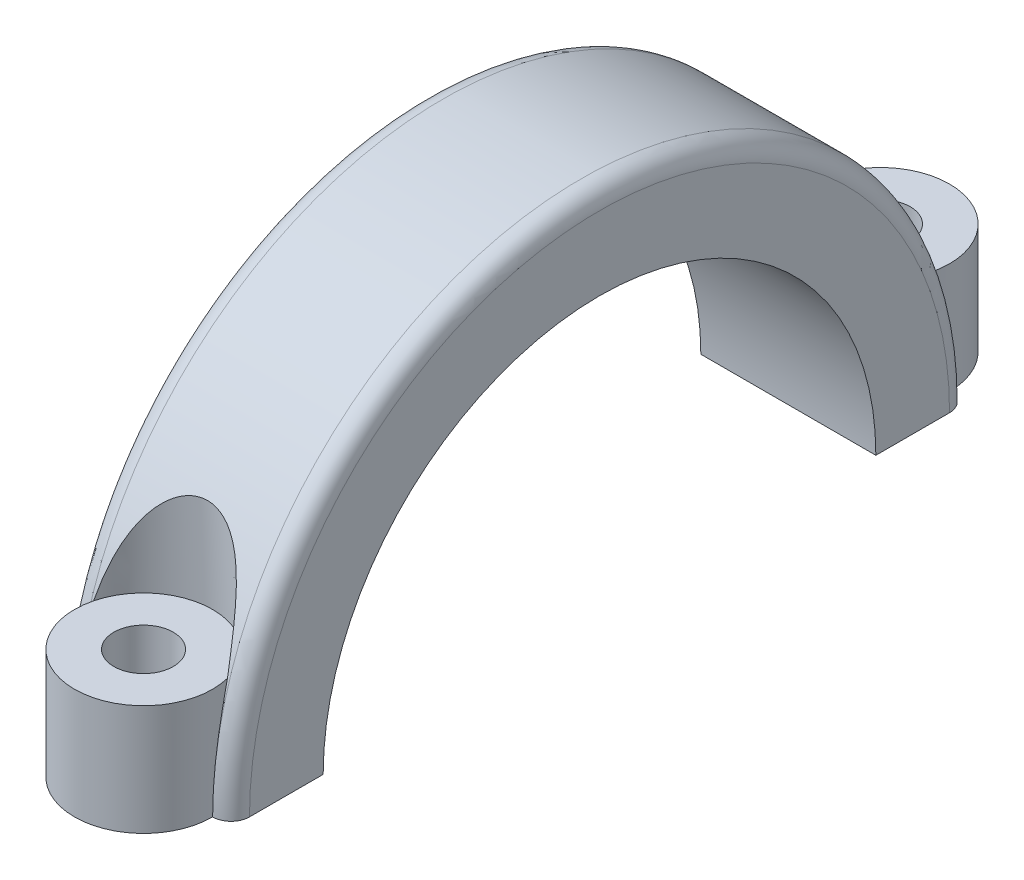
SolidWorks part; units mm, degrees
ref_plane "Front Plane" through (0, 0, 0) normal (0, 0, 1) x (1, 0, 0)
ref_plane "Top Plane" through (0, 0, 0) normal (0, 1, 0) x (1, 0, 0)
ref_plane "Right Plane" through (0, 0, 0) normal (1, 0, 0) x (0, 0, -1)
sketch "Sketch1" plane through (0, 0, 0) normal (1, 0, 0) x (0, 0, -1)
  line L0 (-50.8, 0) -> (-38.1, 0)
  line L1 (38.1, 0) -> (50.8, 0)
  arc A0 (38.1, 0) -> (-38.1, 0) centre (0, 0) ccw
  arc A1 (50.8, 0) -> (-50.8, 0) centre (0, 0) ccw
  circle A3 centre (0, 0) radius 38.1 construction
  circle A4 centre (0, 0) radius 50.8 construction
  point P1 (50.8, 0)
  point P7 (36.4352, 11.1394)
  dimension "D1" = 76.2
  dimension "D2" = 12.7
extrude "Boss-Extrude1" add sketch "Sketch1" along normal mid plane 24.13
sketch "Sketch2" plane through (0, 0, 0) normal (0, -1, 0) x (1, 0, 0)
  line L0 (12.065, -50.8) -> (-12.065, -50.8) construction
  circle A0 centre (0, -50.8) radius 9.525
  dimension "D1" = 19.05
extrude "Boss-Extrude2" add sketch "Sketch2" against normal blind 15.25
extrude "Cut-Extrude1" cut sketch "Sketch2<2>" against normal blind 15.25 draft 3 from offset 15.25 offset against normal yes
sketch "Sketch2<2>" plane through (0, 0, 0) normal (0, -1, 0) x (1, 0, 0) same geometry as "Sketch2"
hole_wizard "CBORE for 5/16 Socket Head Cap Screw1" positions "Sketch3" profile "Sketch4" counterbore size "5/16" standard "ANSI Inch" end condition through all
sketch "Sketch3" plane through (0, 0, 0) normal (0, -1, 0) x (-1, 0, 0)
  point P0 (0, 50.8)
sketch "Sketch4" plane through (0, 0, -50.8) normal (1, 0, 0) x (0, 0, -1)
  line L0 (0, 0) -> (0, 50.8)
  line L1 (0, 50.8) -> (4.1021, 50.8)
  line L3 (4.1021, 50.8) -> (4.1021, 7.9375)
  line L4 (4.1021, 7.9375) -> (6.7475, 7.9375)
  line L5 (6.7475, 7.9375) -> (6.7475, 0)
  line L7 (6.7475, 0) -> (0, 0)
  line L11 (0, -6.35) -> (0, 107.95) construction
  dimension "Thru Hole Dia." = 8.2042
  dimension "Thru Hole Depth" = 50.8
  dimension "C'Bore Dia." = 13.495
  dimension "C'Bore Depth" = 7.9375
mirror "Mirror1" about plane through (0, 0, 0) normal (0, 0, 1) of "Boss-Extrude2", "CBORE for 5/16 Socket Head Cap Screw1"
mirror "Mirror2" about plane through (0, 0, 0) normal (0, 0, 1) of "Cut-Extrude1"
fillet "Fillet1" radius 2.54 2 edges at (12.065, 50.8, 0) (-12.065, 50.8, 0)
